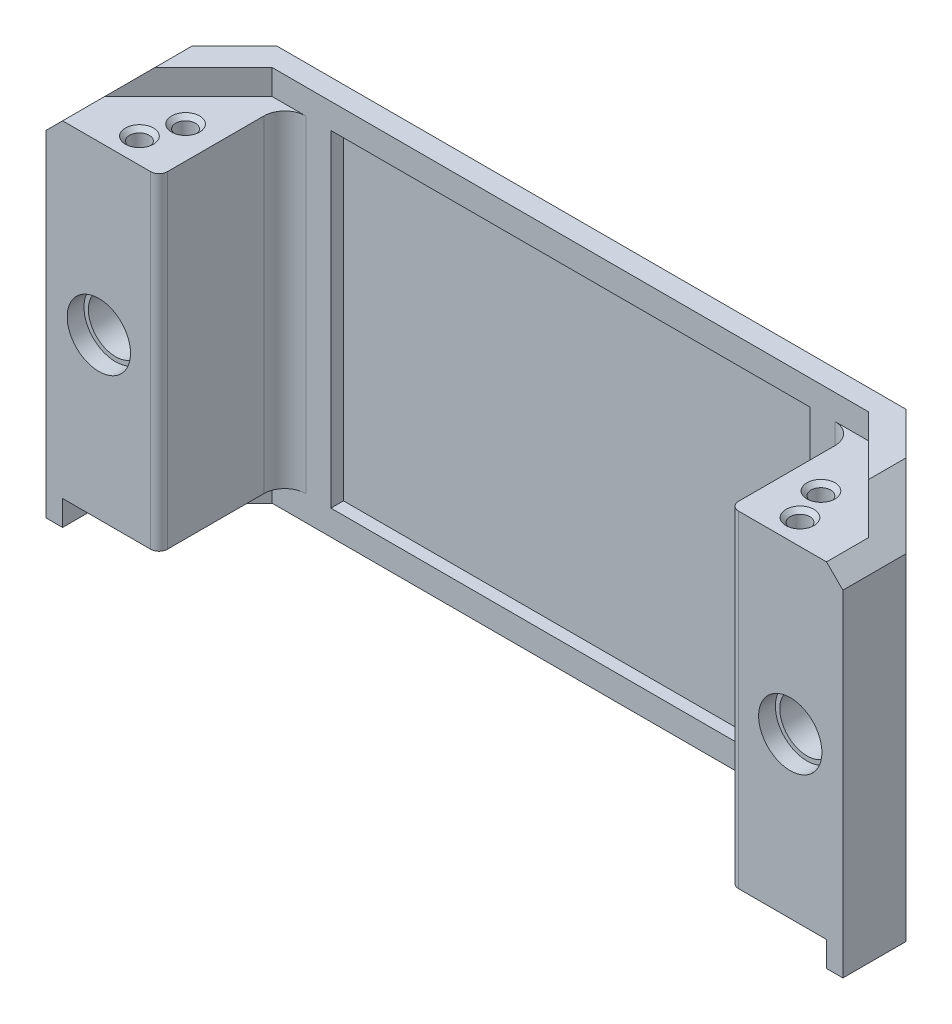
SolidWorks part; units mm, degrees
ref_plane "Front Plane" through (0, 0, 0) normal (0, 0, 1) x (1, 0, 0)
ref_plane "Top Plane" through (0, 0, 0) normal (0, 1, 0) x (1, 0, 0)
ref_plane "Right Plane" through (0, 0, 0) normal (1, 0, 0) x (0, 0, -1)
sketch "Sketch1" plane through (0, 0, 0) normal (0, 0, 1) x (1, 0, 0)
  line L1 (-95, 45) -> (95, 45)
  line L2 (-95, 45) -> (-95, -45)
  line L3 (-95, -45) -> (95, -45)
  line L4 (95, 45) -> (95, -45)
  line L5 (-95, 45) -> (95, -45) construction
  line L6 (-95, -45) -> (95, 45) construction
  point P0 (0, 0)
  point P6 (0, 0)
  dimension "D2" = 190
  dimension "D4" = 90
extrude "Boss-Extrude1" add sketch "Sketch1" along normal blind 5
sketch "Sketch2" plane through (0, 0, 5) normal (0, 0, 1) x (1, 0, 0)
  line L0 (-95, -45) -> (95, -45) construction
  line L1 (-95, 45) -> (-91.1, 45)
  line L2 (-95, 45) -> (-95, -45)
  line L3 (-95, -45) -> (-91.1, -45)
  line L4 (-91.1, 45) -> (-91.1, -45)
  line L5 (0, 0) -> (0, 45) construction
  line L6 (95, 45) -> (-95, 45) construction
  line L7 (95, -45) -> (91.1, -45)
  line L8 (91.1, 45) -> (91.1, -45)
  line L9 (95, 45) -> (91.1, 45)
  line L10 (95, 45) -> (95, -45)
  dimension "D1" = 3.9
extrude "Boss-Extrude2" add sketch "Sketch2" along normal blind 30
sketch "Sketch3" plane through (0, 45, 0) normal (0, 1, 0) x (1, 0, 0)
  line L0 (-91.1, -35) -> (-91.1, -5) construction
  line L1 (-91.1, -14) -> (-57.1, -14)
  line L2 (-91.1, -14) -> (-91.1, -19)
  line L3 (-91.1, -19) -> (-57.1, -19)
  line L4 (-57.1, -14) -> (-57.1, -19)
  line L5 (91.1, -35) -> (91.1, -5) construction
  line L6 (91.1, -14) -> (44.1, -14)
  line L7 (91.1, -14) -> (91.1, -19)
  line L8 (91.1, -19) -> (44.1, -19)
  line L9 (44.1, -14) -> (44.1, -19)
  line L10 (91.1, -5) -> (-91.1, -5) construction
  dimension "D1" = 9
  dimension "D2" = 9
  dimension "D3" = 5
  dimension "D4" = 5
  dimension "D5" = 34
  dimension "D6" = 47
extrude "Boss-Extrude3" add sketch "Sketch3" against normal up to surface (90 mm away) up to face at (0, -45, 18.75)
sketch "Sketch4" plane through (0, 0, 19) normal (0, 0, 1) x (1, 0, 0)
  line L0 (91.1, -45) -> (91.1, 45) construction
  line L1 (-91.1, 45) -> (91.1, 45)
  line L2 (-91.1, 45) -> (-91.1, 39)
  line L3 (-91.1, 39) -> (91.1, 39)
  line L4 (91.1, 45) -> (91.1, 39)
  line L5 (0, 0) -> (-91.1, 0) construction
  line L6 (-91.1, -45) -> (-91.1, 45) construction
  line L7 (-91.1, -39) -> (91.1, -39)
  line L8 (91.1, -45) -> (91.1, -39)
  line L9 (-91.1, -45) -> (91.1, -45)
  line L10 (-91.1, -45) -> (-91.1, -39)
  dimension "D1" = 6
extrude "Cut-Extrude1" cut sketch "Sketch4" against normal blind 5
chamfer "Chamfer6" distance 20 angle 45 4 edges at (91.1, 0, 5) (95, 0, 0) (-95, 0, 0) (-91.1, 0, 5)
sketch "Sketch7" plane through (0, 39, 0) normal (0, 1, 0) x (1, 0, 0)
  line L0 (-85.1, -19) -> (-91.1, -25)
  line L1 (-91.1, -25) -> (-91.1, -35)
  line L2 (-91.1, -35) -> (-68.1, -35)
  line L3 (-68.1, -35) -> (-68.1, -19)
  line L4 (-85.1, -19) -> (-57.1, -19) construction
  line L5 (-68.1, -19) -> (-85.1, -19)
  line L6 (0, 0) -> (0, -5) construction
  line L7 (71.1, -5) -> (-71.1, -5) construction
  line L8 (68.1, -35) -> (68.1, -19)
  line L9 (91.1, -35) -> (68.1, -35)
  line L10 (91.1, -25) -> (91.1, -35)
  line L11 (85.1, -19) -> (91.1, -25)
  line L12 (68.1, -19) -> (85.1, -19)
  dimension "D1" = 23
extrude "Boss-Extrude4" add sketch "Sketch7" against normal up to surface (78 mm away) up to face at (-69.85, -39, 16.5)
fillet "Fillet5" radius 2 2 edges at (-68.1, 0, 35) (68.1, 0, 35)
sketch "Sketch9" plane through (0, 0, 35) normal (0, 0, 1) x (1, 0, 0)
  line L6 (0, 0) -> (0, -45) construction
  line L7 (-71.1, -45) -> (71.1, -45) construction
  line L8 (-95, 45) -> (-95, -45) construction
  line L9 (-95, 39) -> (-82.45, 39) construction
  line L10 (-95, 39) -> (-95, -0.9074) construction
  line L11 (-95, -0.9074) -> (-82.45, -0.9074) construction
  line L12 (-82.45, 39) -> (-82.45, -0.9074) construction
  line L13 (-91.1, 39) -> (-70.1, 39) construction
  circle A0 centre (-82.45, -0.9074) radius 6.5
  circle A1 centre (82.45, -0.9074) radius 6.5
  dimension "D3" = 13
  dimension "D1" = 39.9074
  dimension "D2" = 12.55
extrude "Cut-Extrude4" cut sketch "Sketch9" against normal blind 10
sketch "Sketch10" plane through (0, 0, 35) normal (0, 0, 1) x (1, 0, 0)
  circle A0 centre (-82.45, -0.9074) radius 7.55
  circle A1 centre (82.45, -0.9074) radius 7.55
  dimension "D1" = 15.1
  dimension "D2" = 15.1
extrude "Cut-Extrude5" cut sketch "Sketch10" against normal blind 4
sketch "Sketch15" plane through (0, 39, 0) normal (0, 1, 0) x (1, 0, 0)
  line L0 (68.1, -19) -> (68.1, -33) construction
  line L5 (80.1, -14) -> (44.1, -14) construction
  line L6 (91.1, -35) -> (68.1, -35) construction
  line L7 (91.1, -35) -> (91.1, -14) construction
  line L8 (91.1, -14) -> (68.1, -14) construction
  line L9 (68.1, -35) -> (68.1, -14) construction
  line L10 (68.1, -14) -> (75.7667, -21) construction
  line L11 (75.7667, -21) -> (83.4333, -28) construction
  line L12 (83.4333, -28) -> (91.1, -35) construction
  line L13 (0, 0) -> (0, -5) construction
  line L14 (71.1, -5) -> (-71.1, -5) construction
  line L15 (75.7667, -21) -> (75.7667, -29) construction
  line L16 (75.7667, -29) -> (78.7667, -29) construction
  circle A0 centre (75.7667, -21) radius 2.35
  circle A1 centre (83.4333, -28) radius 2.35 construction
  circle A2 centre (-75.7667, -21) radius 2.35
  circle A3 centre (-83.4333, -28) radius 2.35 construction
  circle A6 centre (78.7667, -29) radius 2.35
  circle A7 centre (-78.7667, -29) radius 2.35
  dimension "D1" = 4.7
  dimension "D2" = 4.7
  dimension "D5" = 4.7
  dimension "D3" = 23
  dimension "D4" = 21
  dimension "D6" = 8
  dimension "D7" = 3
extrude "Cut-Extrude7" cut sketch "Sketch15" against normal blind 8
chamfer "Chamfer7" distance 1 angle 45 4 edges at (-75.7667, 39, 18.65) (75.7667, 39, 23.35) (-78.7667, 39, 26.65) (78.7667, 39, 31.35)
sketch "Sketch17" plane through (0, -39, 0) normal (0, -1, 0) x (1, 0, 0)
  line L0 (0, 0) -> (0, 5) construction
  line L1 (91.1, 35) -> (68.1, 35) construction
  line L2 (91.1, 35) -> (91.1, 19) construction
  line L3 (91.1, 19) -> (68.1, 19) construction
  line L4 (68.1, 35) -> (68.1, 19) construction
  line L5 (-71.1, 5) -> (71.1, 5) construction
  line L6 (68.1, 33) -> (68.1, 19) construction
  line L7 (68.1, 19) -> (44.1, 19) construction
  circle A0 centre (79.6, 27) radius 6.1
  circle A1 centre (-79.6, 27) radius 6.1
  dimension "D2" = 12.2
  dimension "D1" = 11.5
  dimension "D3" = 8
  dimension "D4" = 11.5
extrude "Cut-Extrude8" cut sketch "Sketch17" against normal blind 3.2
fillet "Fillet7" radius 0.2 2 edges at (-85.7, -39, 27) (85.7, -39, 27)
chamfer "Chamfer8" distance 9.9 angle 45 2 edges at (-95, 45, 27.5) (95, 45, 27.5)
sketch "Sketch18" plane through (-57.1, 0, 0) normal (1, 0, 0) x (0, 0, -1)
  line L1 (-19, 39) -> (-14, 39)
  line L2 (-19, 39) -> (-19, -39)
  line L3 (-19, -39) -> (-14, -39)
  line L4 (-14, 39) -> (-14, -39)
extrude "Cut-Extrude9" cut sketch "Sketch18" against normal up to surface and the other way up to surface up to face at (-68.1, 0, 26) other way up to face at (68.1, 0, 26)
sketch "Sketch20" plane through (0, 39, 0) normal (0, 1, 0) x (1, 0, 0)
  line L0 (-68.1, -14) -> (-68.1, -5)
  line L1 (71.1, -5) -> (-71.1, -5) construction
  line L2 (-68.1, -5) -> (-71.1, -5)
  line L3 (-71.1, -5) -> (-80.1, -14)
  line L4 (-80.1, -14) -> (-68.1, -14)
  line L5 (0, 0) -> (0, -5) construction
  line L6 (71.1, -5) -> (80.1, -14)
  line L7 (68.1, -5) -> (71.1, -5)
  line L8 (68.1, -14) -> (68.1, -5)
  line L9 (80.1, -14) -> (68.1, -14)
extrude "Boss-Extrude5" add sketch "Sketch20" against normal up to surface (78 mm away) up to face at (-85.9, -39, 27)
fillet "Fillet8" radius 5 2 edges at (68.1, 0, 5) (-68.1, 0, 5)
sketch "Sketch21" plane through (0, 0, 5) normal (0, 0, 1) x (1, 0, 0)
  line L0 (-71.1, -45) -> (71.1, -45) construction
  line L1 (-57.1, 39) -> (57.1, 39)
  line L2 (-57.1, 39) -> (-57.1, -39)
  line L3 (-57.1, -39) -> (57.1, -39)
  line L4 (57.1, 39) -> (57.1, -39)
  line L5 (71.1, 45) -> (-71.1, 45) construction
  line L6 (-63.1, 39) -> (-63.1, -39) construction
  line L7 (63.1, -39) -> (63.1, 39) construction
  dimension "D1" = 6
  dimension "D2" = 6
  dimension "D3" = 6
  dimension "D4" = 6
extrude "Cut-Extrude10" cut sketch "Sketch21" against normal blind 3
sketch "Sketch22" plane through (0, 0, 2) normal (0, 0, 1) x (1, 0, 0)
  line L0 (0, 39) -> (0, -39)
  line L1 (57.1, 39) -> (-57.1, 39) construction
  line L2 (-57.1, -39) -> (57.1, -39) construction
